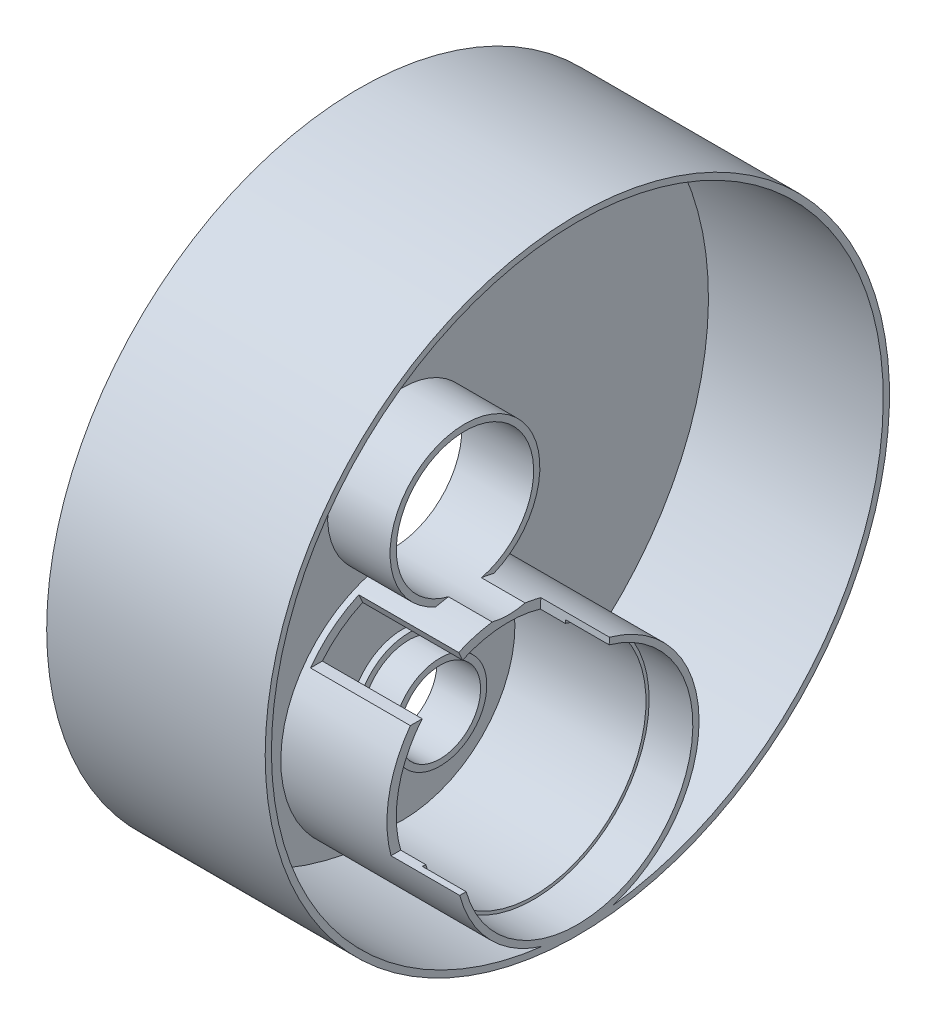
SolidWorks part; units mm, degrees
material "1060 Сплав"
ref_plane "Спереди" through (0, 0, 0) normal (0, 0, 1) x (1, 0, 0)
ref_plane "Сверху" through (0, 0, 0) normal (0, 1, 0) x (1, 0, 0)
ref_plane "Справа" through (0, 0, 0) normal (1, 0, 0) x (0, 0, -1)
sketch "Эскиз1" plane through (0, 0, 0) normal (0, 0, 1) x (1, 0, 0)
  line L0 (0, 0) -> (26039.5549, 0) construction
  line L1 (-27, 7.5) -> (-27, 8.5)
  line L2 (0, 19.5) -> (-29, 19.5)
  line L3 (-29, 19.5) -> (-29, 6.5)
  line L4 (-29, 6.5) -> (-22, 6.5)
  line L5 (-22, 6.5) -> (-22, 7.5)
  line L6 (-22, 7.5) -> (-27, 7.5)
  line L7 (-28, 8.5) -> (-28, 18)
  line L8 (-28, 18) -> (-7, 18)
  line L9 (-7, 18) -> (-7, 18.5)
  line L10 (-7, 18.5) -> (0, 18.5)
  line L11 (0, 18.5) -> (0, 19.5)
  line L12 (-27, 8.5) -> (-28, 8.5)
  dimension "D1" = 18.5
  dimension "D2" = 1
  dimension "D3" = 18
  dimension "D4" = 7
  dimension "D5" = 21
  dimension "D6" = 1
  dimension "D7" = 1
  dimension "D8" = 1
  dimension "D9" = 7.5
  dimension "D10" = 1
  dimension "D11" = 13
  dimension "D12" = 0.5
  dimension "D13" = 5
revolve "Повернуть1" add sketch "Эскиз1" angle 360 about L0
sketch "Эскиз2" plane through (0, 0, 0) normal (1, 0, 0) x (0, 0, -1)
  line L0 (0, 0) -> (0, 50000) construction
  line L1 (5.1563, 18.8059) -> (5, 16.2481)
  line L2 (5, 0) -> (5, 50000) construction
  line L3 (0, 0) -> (0, -5) construction
  line L4 (0, -5) -> (-50000, -5) construction
  line L5 (-18.8481, -5) -> (-16.2481, -5)
  line L6 (-5, 0) -> (-5, 50000) construction
  arc A0 (5, 16.2481) -> (-16.2481, -5) centre (0, 0) ccw
  arc A1 (-18.8481, -5) -> (5.1563, 18.8059) centre (0, 0) cw
  circle A2 centre (0, 0) radius 19.5 construction
  dimension "D3" = 17
  dimension "D4" = 19.5
  dimension "D1" = 5
  dimension "D2" = 5
  dimension "D5" = 2.5626
  dimension "D6" = 0
extrude "Вырез-Вытянуть1" cut sketch "Эскиз2" against normal blind 11 contours A0 L5 A1 L1
sketch "Эскиз3" plane through (0, 0, 0) normal (1, 0, 0) x (0, 0, -1)
  line L3 (-40, 11.5) -> (-12.52, 11.5)
  line L4 (0, 0) -> (-20535.6471, 45588.2353) construction
  line L5 (-6.9821, 15.5) -> (-13.2408, 29.394)
  line L6 (-13.2408, 29.394) -> (-40, 11.5)
  line L7 (0, 15.5) -> (-50000, 15.5) construction
  circle A0 centre (0, 0) radius 15.5 construction
  circle A1 centre (0, 0) radius 11.5 construction
  arc A2 (-6.9821, 15.5) -> (-12.52, 11.5) centre (0, 0) ccw
  dimension "D1" = 31
  dimension "D2" = 23
  dimension "D4" = 34
  dimension "D3" = 15.2386
  dimension "D5" = 32.1908
extrude "Вырез-Вытянуть2" cut sketch "Эскиз3" against normal blind 27
sketch "Эскиз4" plane through (-29, 0, 0) normal (-1, 0, 0) x (0, 0, 1)
  circle A1 centre (0, 30) radius 50
  circle A3 centre (0, 0) radius 6.5 construction
  circle A4 centre (0, 0) radius 6.5
  dimension "D2" = 100
  dimension "D5" = 13
  dimension "D1" = 30
  dimension "D4" = 30
extrude "Бобышка-Вытянуть1" add sketch "Эскиз4" against normal blind 1
sketch "Эскиз5" plane through (-29, 0, 0) normal (-1, 0, 0) x (0, 0, 1)
  circle A0 centre (0, 30) radius 50
  circle A1 centre (0, 30) radius 49
  point P4 (-4.872, 28.916)
  point P5 (0, 30)
  dimension "D1" = 100
  dimension "D2" = 98
extrude "Бобышка-Вытянуть2" add sketch "Эскиз5" against normal blind 29 and the other way blind 6
sketch "Эскиз15" plane through (-28, 0, 0) normal (-1, 0, 0) x (0, 0, 1)
  circle A0 centre (0, 30) radius 11
  circle A1 centre (0, 30) radius 12
  point P4 (-16.2271, 33.6223)
  point P5 (0, 30)
  dimension "D1" = 1
  dimension "D2" = 24
extrude "Бобышка-Вытянуть3" add sketch "Эскиз15" against normal blind 10 and the other way blind 1.5
sketch "Эскиз16" plane through (-28, 0, 0) normal (1, 0, 0) x (0, 0, -1)
  circle A0 centre (0, 30) radius 11
  arc A1 (2.6373, 19.3208) -> (-2.6373, 19.3208) centre (0, 30) ccw construction
extrude "Вырез-Вытянуть4" cut sketch "Эскиз16" against normal through all both and the other way through all
sketch "Эскиз12" plane through (-29, 0, 0) normal (-1, 0, 0) x (0, 0, 1)
  line L0 (0, 30) -> (26.4, 30) construction
  circle A0 centre (26.4, 30) radius 5
  point P4 (0, 30)
  dimension "D2" = 10
  dimension "D1" = 26.4
extrude "Вырез-Вытянуть3" cut sketch "Эскиз12" against normal up to next
hole_wizard "Сверление под метчик M2x0.41" positions "Эскиз13" profile "Эскиз14" hole size "M2x0.4" standard "Ansi Metric" end condition through all
sketch "Эскиз13" plane through (-29, 0, 0) normal (-1, 0, 0) x (0, 0, 1)
  line L0 (26.4, 30) -> (26.4, 36.5) construction
  point P0 (26.4, 36.5)
  dimension "D1" = 6.5
sketch "Эскиз14" plane through (-29, 36.5, 26.4) normal (0, 1, 0) x (0, 0, 1)
  line L0 (0, 0) -> (0, 29)
  line L1 (0, 29) -> (0.8, 29)
  line L2 (0.8, 29) -> (0.8, 0)
  line L5 (0.8, 0) -> (0, 0)
  line L11 (0, -6.35) -> (0, 107.95) construction
  dimension "Диаметр сквозного отверстия" = 1.6
  dimension "Глубина сквозного отверстия" = 29
pattern_circular "Круговой массив1" count 3 over 360 about axis through (0.001, 30, 26.4) along (-1, 0, 0) of "Сверление под метчик M2x0.41"
